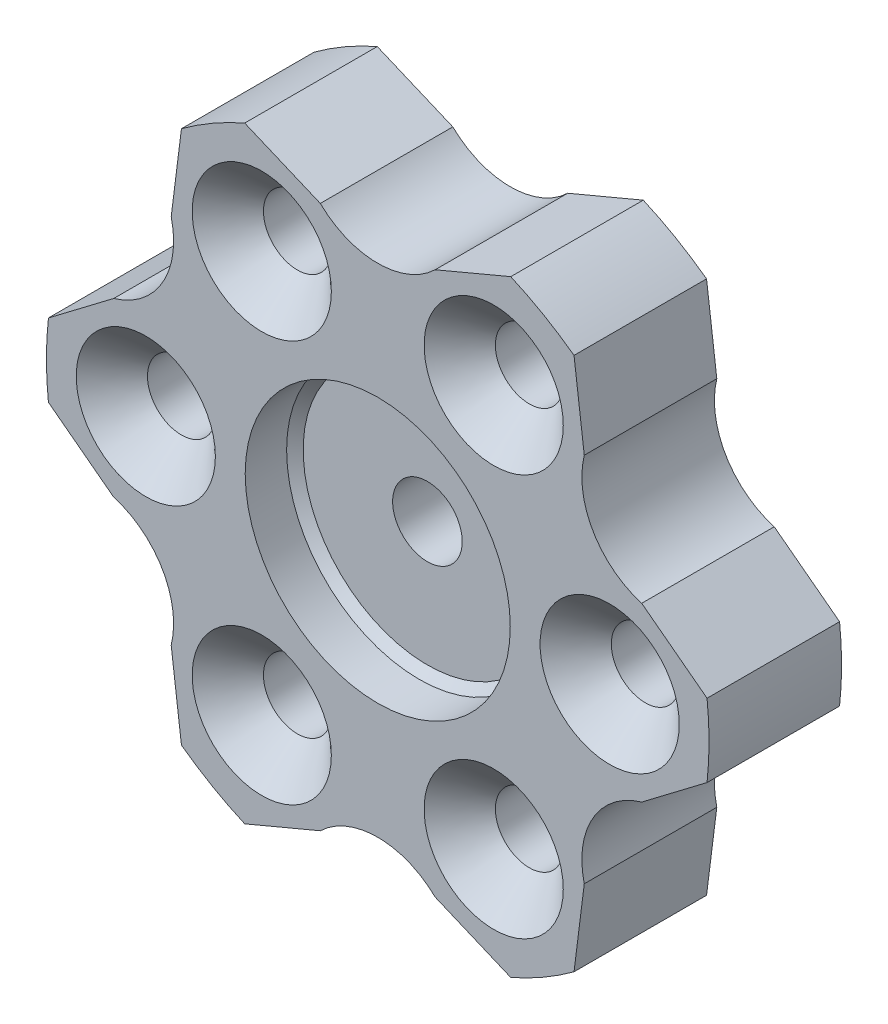
SolidWorks part; units mm, degrees
material "Plain Carbon Steel"
ref_plane "Front Plane" through (0, 0, 0) normal (0, 0, 1) x (1, 0, 0)
ref_plane "Top Plane" through (0, 0, 0) normal (0, 1, 0) x (1, 0, 0)
ref_plane "Right Plane" through (0, 0, 0) normal (1, 0, 0) x (0, 0, -1)
sketch "Sketch1" plane through (0, 0, 0) normal (0, 0, 1) x (1, 0, 0)
  circle A0 centre (0, 0) radius 20
  dimension "D1" = 40
extrude "Boss-Extrude1" add sketch "Sketch1" along normal blind 8
hole_wizard "CSK for M4 Countersunk Flat Head Screw1" positions "Sketch9" profile "Sketch10" countersink size "M4" standard "ISO" end condition through all
sketch "Sketch9" plane through (0, 0, 8) normal (0, 0, 1) x (1, 0, 0)
  circle A0 centre (0, 0) radius 14 construction
  point P0 (7, 12.1244)
  point P2 (-14, 0)
  point P4 (-7, 12.1244)
  point P6 (-7, -12.1244)
  point P8 (14, 0)
  point P10 (7, -12.1244)
  dimension "D6" = 28
  dimension "D1" = 60
  dimension "D2" = 60
  dimension "D3" = 60
  dimension "D4" = 60
  dimension "D5" = 60
sketch "Sketch10" plane through (7, 12.1244, 8) normal (1, 0, 0) x (0, -1, 0)
  line L0 (0, 0) -> (0, 8)
  line L1 (0, 8) -> (2.05, 8)
  line L2 (2.05, 8) -> (2.05, 2.15)
  line L3 (2.05, 2.15) -> (4.2, 0)
  line L5 (4.2, 0) -> (0, 0)
  line L6 (-2.05, 2.15) -> (-4.2, 0) construction
  line L11 (0, -6.35) -> (0, 107.95) construction
  dimension "Thru Hole Dia." = 4.1
  dimension "Thru Hole Depth" = 8
  dimension "Near C'Sink Dia." = 8.4
  dimension "Near C'Sink Angle" = 90
sketch "Sketch11" plane through (0, 0, 8) normal (0, 0, 1) x (1, 0, 0)
  circle A0 centre (0, 0) radius 8
  dimension "D1" = 16
extrude "Cut-Extrude3" cut sketch "Sketch11" against normal blind 3
hole_wizard "M5 Tapped Hole1" positions "Sketch12" profile "Sketch13" tap size "M5" standard "ISO" end condition through all
sketch "Sketch12" plane through (0, 0, 5) normal (0, 0, 1) x (1, 0, 0)
  point P0 (0, 0)
sketch "Sketch13" plane through (0, 0, 5) normal (1, 0, 0) x (0, -1, 0)
  line L0 (0, 0) -> (0, 5)
  line L1 (0, 5) -> (2.1, 5)
  line L2 (2.1, 5) -> (2.1, 0)
  line L5 (2.1, 0) -> (0, 0)
  line L11 (0, -6.35) -> (0, 107.95) construction
  dimension "Thru Tap Drill Dia." = 4.2
  dimension "Thru Tap Drill Depth" = 5
cosmetic thread "Hole Thread1" parameters "D2"=5
chamfer "Chamfer1" distance 0.5 angle 45 1 edges at (8, 0, 5)
sketch "Sketch14" plane through (0, 0, 8) normal (0, 0, 1) x (1, 0, 0)
  line L0 (0, 0) -> (-20, 0) construction
  circle A0 centre (-17.3205, 10) radius 5
  circle A1 centre (0, 0) radius 20 construction
  circle A2 centre (0, 20) radius 5
  circle A3 centre (17.3205, 10) radius 5
  circle A4 centre (17.3205, -10) radius 5
  circle A5 centre (0, -20) radius 5
  circle A6 centre (-17.3205, -10) radius 5
  point P19 (0, 0)
  dimension "D2" = 10
  dimension "D1" = 30
  dimension "D3" = 6
extrude "Cut-Extrude4" cut sketch "Sketch14" against normal up to surface (8 mm away) up to face at (2.1, 0, 0)
chamfer "Chamfer2" distance 2.5 angle 60 12 edges at (4.9608, 19.375, 4) (-4.9608, 19.375, 4) (14.2989, 13.9837, 4) (19.2596, 5.3913, 4) (19.2596, -5.3913, 4) (14.2989, -13.9837, 4) (4.9608, -19.375, 4) (-4.9608, -19.375, 4) (-14.2989, -13.9837, 4) (-19.2596, -5.3913, 4) (-19.2596, 5.3913, 4) (-14.2989, 13.9837, 4) first distance on face at (0, 17.1875, 4) first distance on face at (14.8848, 8.5938, 4) first distance on face at (14.8848, -8.5937, 4) first distance on face at (0, -17.1875, 4) first distance on face at (-14.8848, -8.5938, 4) first distance on face at (-14.8848, 8.5938, 4)
